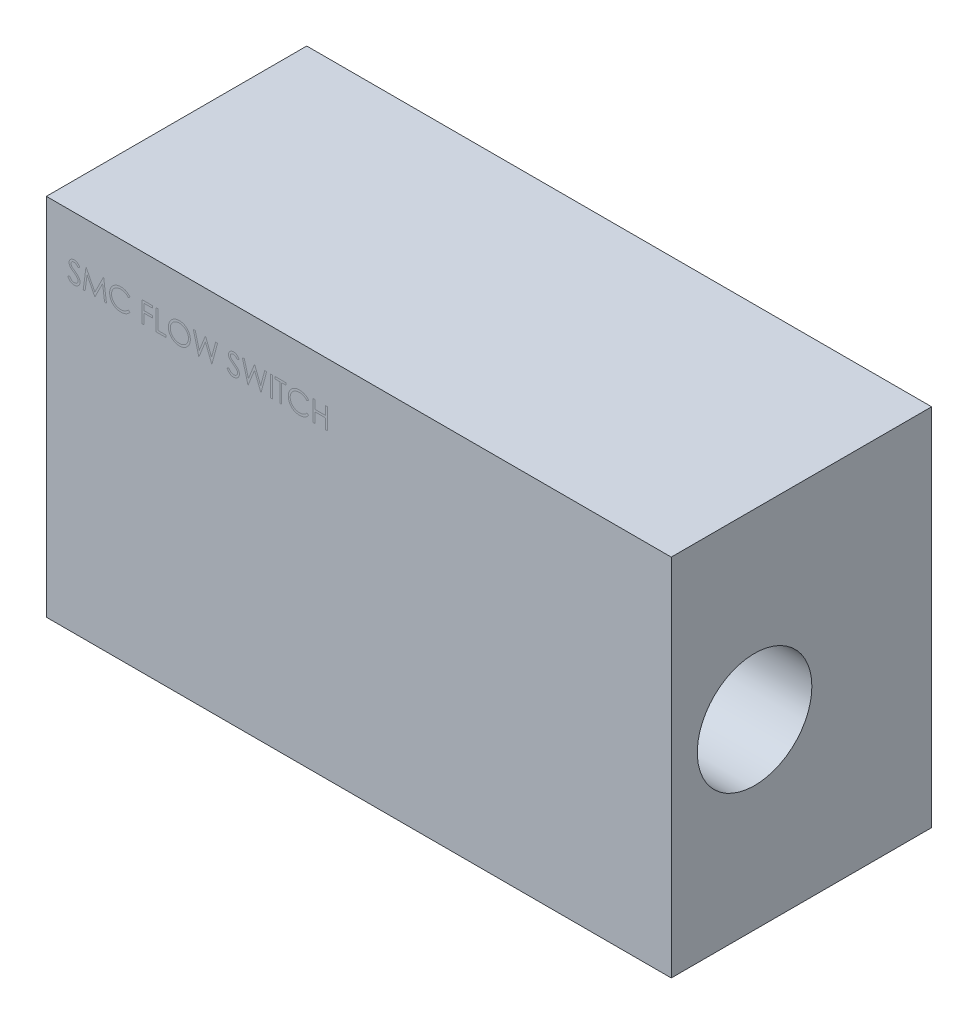
SolidWorks part; units mm, degrees
ref_plane "Front Plane" through (0, 0, 0) normal (0, 0, 1) x (1, 0, 0)
ref_plane "Top Plane" through (0, 0, 0) normal (0, 1, 0) x (1, 0, 0)
ref_plane "Right Plane" through (0, 0, 0) normal (1, 0, 0) x (0, 0, -1)
sketch "Sketch1" plane through (0, 0, 0) normal (0, 0, 1) x (1, 0, 0)
  line L1 (-30, 17.5) -> (30, 17.5)
  line L2 (-30, 17.5) -> (-30, -17.5)
  line L3 (-30, -17.5) -> (30, -17.5)
  line L4 (30, 17.5) -> (30, -17.5)
  line L5 (0, -17.5) -> (0, 17.5) construction
  line L6 (-30, 0) -> (30, 0) construction
  point P0 (0, 0)
  dimension "D1" = 60
  dimension "D2" = 35
extrude "Boss-Extrude1" add sketch "Sketch1" along normal mid plane 25
sketch "Sketch2" plane through (0, 0, 12.5) normal (0, 0, 1) x (1, 0, 0)
  line L0 (-28, 11.5) -> (-3, 11.5) construction
  line L1 (-30, 17.5) -> (-30, -17.5) construction
  line L2 (30, 17.5) -> (-30, 17.5) construction
  text T0 "SMC FLOW SWITCH" font "Century Gothic" height 2
  dimension "D1" = 25
  dimension "D2" = 2
  dimension "D3" = 6
wrap "Wrap1" sketch "Sketch2" wrap type scribe source sketch "Sketch2" face at (0, 0, 12.5)
hole_wizard "M10 Clearance Hole1" positions "Sketch3" profile "Sketch4" hole size "M10" standard "ISO"
sketch "Sketch3" plane through (30, 0, 0) normal (1, 0, 0) x (0, 0, -1)
  line L0 (-12.5, -17.5) -> (-12.5, 17.5) construction
  line L1 (-12.5, -17.5) -> (12.5, -17.5) construction
  point P0 (-4.5, 0)
  dimension "D1" = 8
  dimension "D2" = 17.5
sketch "Sketch4" plane through (30, 0, 4.5) normal (0, 1, 0) x (0, 0, -1)
  line L0 (0, 0) -> (0, 11.3047)
  line L1 (0, 11.3047) -> (5.5, 8)
  line L2 (5.5, 8) -> (5.5, 0)
  line L5 (5.5, 0) -> (0, 0)
  line L10 (0, 11.3047) -> (-5.5, 8) construction
  line L11 (0, -6.35) -> (0, 107.95) construction
  dimension "Hole Dia." = 11
  dimension "Hole Depth" = 8
  dimension "Drill Angle" = 118
